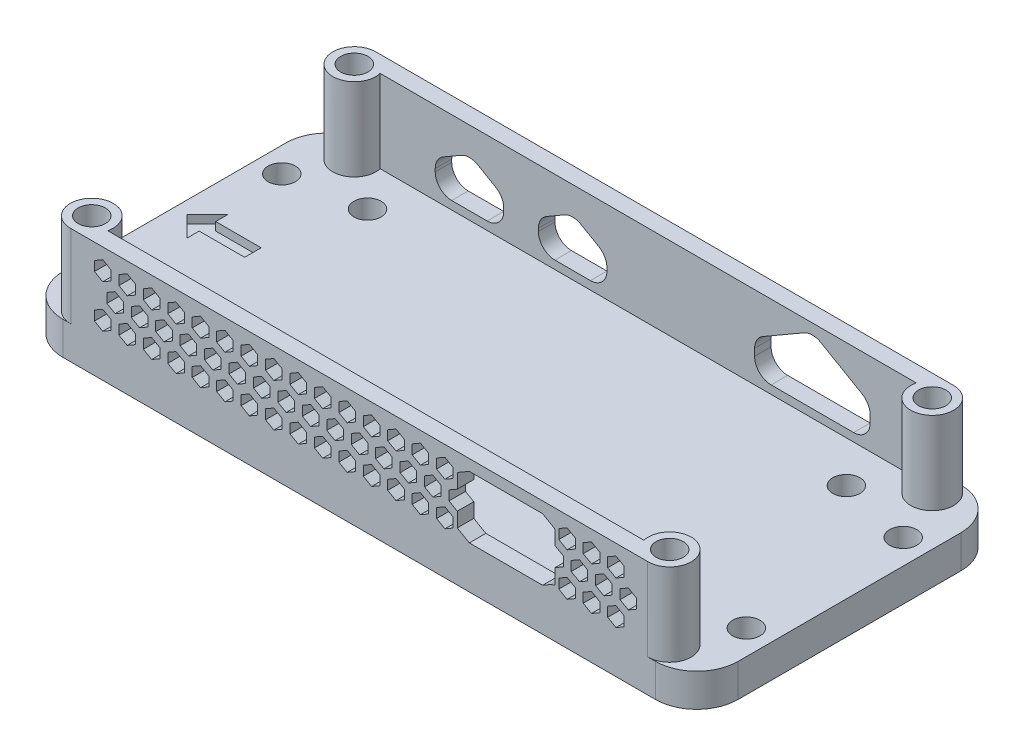
SolidWorks part; units mm, degrees
ref_plane "Płaszczyzna przednia" through (0, 0, 0) normal (0, 0, 1) x (1, 0, 0)
ref_plane "Płaszczyzna górna" through (0, 0, 0) normal (0, 1, 0) x (1, 0, 0)
ref_plane "Płaszczyzna prawa" through (0, 0, 0) normal (1, 0, 0) x (0, 0, -1)
sketch "Szkic1" plane through (0, 0, 0) normal (0, 1, 0) x (1, 0, 0)
  line L0 (-40.885, 0) -> (-37.885, 0) construction
  line L1 (-40.885, -18.5) -> (40.885, -18.5)
  line L2 (-40.885, -18.5) -> (-40.885, 18.5)
  line L3 (-40.885, 18.5) -> (40.885, 18.5)
  line L4 (40.885, -18.5) -> (40.885, 18.5)
  line L5 (-40.885, -18.5) -> (40.885, 18.5) construction
  line L6 (-40.885, 18.5) -> (40.885, -18.5) construction
  line L7 (-37.885, 0) -> (-37.885, 10) construction
  line L8 (-55, 0) -> (55, 0) construction
  line L10 (40.885, 0) -> (37.885, 0) construction
  line L11 (37.885, 0) -> (37.885, 9.5) construction
  circle A2 centre (-37.885, 10) radius 1.65
  circle A3 centre (-37.885, -10) radius 1.65
  circle A6 centre (37.885, 9.5) radius 1.65
  circle A7 centre (37.885, -9.5) radius 1.65
  point P0 (0, 0)
  dimension "D1" = 10
  dimension "D2" = 3.3
  dimension "D6" = 3.3
  dimension "D3" = 3
  dimension "D4" = 37
  dimension "D5" = 75.77
  dimension "D7" = 9.5
extrude "Dodanie-wyciągnięcie1" add sketch "Szkic1" along normal blind 4
fillet "Zaokrąglenie1" radius 5 4 edges at (-40.885, 2, -18.5) (40.885, 2, -18.5) (40.885, 2, 18.5) (-40.885, 2, 18.5)
sketch "Szkic2" plane through (0, 4, 0) normal (0, 1, 0) x (1, 0, 0)
  line L0 (-36.235, 10) -> (36.235, 10) construction
  line L1 (36.235, 9.5) -> (36.235, 10) construction
  line L2 (0, 10) -> (0, 0) construction
  line L4 (-29, 11.5) -> (29, 11.5) construction
  line L5 (-29, 11.5) -> (-29, -11.5) construction
  line L6 (-29, -11.5) -> (29, -11.5) construction
  line L7 (29, 11.5) -> (29, -11.5) construction
  line L8 (-29, 11.5) -> (29, -11.5) construction
  line L9 (-29, -11.5) -> (29, 11.5) construction
  circle A0 centre (-37.885, 10) radius 1.65 construction
  circle A1 centre (29, 11.5) radius 1.65
  circle A2 centre (37.885, 9.5) radius 1.65 construction
  circle A3 centre (29, -11.5) radius 1.65
  circle A4 centre (-29, -11.5) radius 1.65
  circle A5 centre (-29, 11.5) radius 1.65
  dimension "D3" = 3.3
  dimension "D4" = 3.3
  dimension "D5" = 3.3
  dimension "D6" = 3.3
  dimension "D1" = 58
  dimension "D2" = 23
extrude "Wytnij-wyciągnięcie11" cut sketch "Szkic2" against normal blind 3.5
ref_plane "Płaszczyzna2" through (0, 0, -11.5) normal (0, 0, -1) x (-1, 0, 0)
sketch "Szkic4" [suppressed] plane through (0, 0, -11.5) normal (0, 0, -1) x (-1, 0, 0)
  line L0 (-29, 4) -> (-28.7, 4) construction
  line L1 (29, 4) -> (-29, 4) construction
  line L2 (29, 4) -> (-29, 4) construction
  line L3 (-28.7, 4) -> (-28.7, 4.2)
  line L4 (-28.7, 4.2) -> (-25.7, 4.2)
  line L5 (-25.7, 4.2) -> (-27.6, 6.1)
  line L6 (-27.6, 6.1) -> (-27.6, 5.9)
  line L7 (-27.6, 5.9) -> (-27.9, 5.6)
  line L8 (-27.9, 5.6) -> (-27.9, 4)
  line L9 (-27.9, 4) -> (-28.7, 4)
  line L10 (-29, 4) -> (-29, 4.3161) construction
  dimension "D1" = 1.6
  dimension "D3" = 0.2
  dimension "D4" = 1.1
  dimension "D5" = 0.3
  dimension "D6" = 135
  dimension "D7" = 135
  dimension "D8" = 1.1
ref_plane "Płaszczyzna3" through (29, 0, 0) normal (1, 0, 0) x (0, 0, -1)
ref_plane "Płaszczyzna4" through (0, 0, 0) normal (-1, 0, 0) x (0, 0, 1)
sketch "Szkic6" plane through (0, 4, 0) normal (0, 1, 0) x (1, 0, 0)
  line L0 (-34.885, -18.5) -> (-34.885, -16.5)
  line L1 (-35.885, -18.5) -> (35.885, -18.5) construction
  line L2 (-34.885, -16.5) -> (34.885, -16.5)
  line L3 (34.885, -16.5) -> (34.885, -18.5)
  line L4 (34.885, -18.5) -> (-34.885, -18.5)
  line L5 (-40.885, 13.5) -> (-40.885, -13.5) construction
  line L6 (40.885, -13.5) -> (40.885, 13.5) construction
  dimension "D1" = 6
  dimension "D2" = 2
  dimension "D3" = 6
extrude "Dodanie-wyciągnięcie2" add sketch "Szkic6" along normal blind 10
mirror "Lustro4" about plane through (0, 0, 0) normal (0, 0, 1) of "Dodanie-wyciągnięcie2"
sketch "Szkic7" plane through (0, 0, -18.5) normal (0, 0, -1) x (-1, 0, 0)
  line L0 (0, 0) -> (5, 0) construction
  line L1 (-35.885, 0) -> (35.885, 0) construction
  line L2 (5, 0) -> (5, 5) construction
  line L3 (5, 5) -> (5, 14)
  line L4 (34.885, 14) -> (-34.885, 14) construction
  line L6 (25.8, 14) -> (25.8, 5)
  line L10 (17.5, 14) -> (25.8, 14)
  line L11 (5, 14) -> (13.3, 14)
  line L12 (13.3, 14) -> (13.3, 5)
  line L13 (13.3, 5) -> (5, 5)
  line L14 (13.3, 5) -> (17.5, 5) construction
  line L15 (17.5, 5) -> (25.8, 5)
  line L16 (17.5, 14) -> (17.5, 5)
  dimension "D1" = 5
  dimension "D2" = 5
  dimension "D3" = 8.3
  dimension "D4" = 8.3
  dimension "D5" = 4.2
extrude "Wytnij-wyciągnięcie1" cut sketch "Szkic7" against normal up to surface (2 mm away) up to face at (0, 9, -16.5)
sketch "Szkic8" plane through (0, 0, -18.5) normal (0, 0, -1) x (-1, 0, 0)
  line L0 (5, 14) -> (5, 8.5)
  line L1 (5, 14) -> (5, 5) construction
  line L2 (5, 8.5) -> (13.3, 8.5) construction
  line L3 (13.3, 5) -> (13.3, 14) construction
  line L4 (9.15, 8.5) -> (9.15, 10.896) construction
  line L5 (5, 8.5) -> (9.15, 10.896)
  line L6 (9.15, 10.896) -> (13.3, 8.5)
  line L7 (13.3, 8.5) -> (13.3, 14)
  line L8 (13.3, 14) -> (5, 14)
  line L9 (15.4, 14) -> (15.4, 5.5312) construction
  line L10 (17.5, 14) -> (13.3, 14) construction
  line L11 (21.65, 8.5) -> (21.65, 10.896) construction
  line L12 (25.8, 8.5) -> (17.5, 8.5) construction
  line L13 (17.5, 14) -> (25.8, 14)
  line L14 (17.5, 8.5) -> (17.5, 14)
  line L15 (21.65, 10.896) -> (17.5, 8.5)
  line L16 (25.8, 8.5) -> (21.65, 10.896)
  line L17 (25.8, 14) -> (25.8, 8.5)
  dimension "D1" = 30
  dimension "D2" = 5.5
extrude "Dodanie-wyciągnięcie3" add sketch "Szkic8" against normal up to surface (2 mm away) up to face at (-10.2667, 9.3333, -16.5)
fillet "Zaokrąglenie2" radius 2 10 edges at (-25.8, 5, -17.5) (-17.5, 5, -17.5) (-13.3, 5, -17.5) (-5, 5, -17.5) (-21.65, 10.896, -17.5) (-9.15, 10.896, -17.5) (-25.8, 8.5, -17.5) (-17.5, 8.5, -17.5) (-13.3, 8.5, -17.5) (-5, 8.5, -17.5)
sketch "Szkic15" plane through (0, 0, -18.5) normal (0, 0, -1) x (-1, 0, 0)
  line L0 (-34.885, 14) -> (-19.885, 14) construction
  line L1 (34.885, 14) -> (-34.885, 14) construction
  line L2 (-19.885, 14) -> (-19.885, 13.0415) construction
  line L3 (-19.885, 13.0415) -> (-12.885, 9)
  line L4 (-12.885, 9) -> (-12.885, 5)
  line L5 (-12.885, 5) -> (-26.885, 5)
  line L6 (-19.885, 13.0415) -> (-19.885, 5) construction
  line L7 (-26.885, 9) -> (-26.885, 5)
  line L8 (-19.885, 13.0415) -> (-26.885, 9)
  line L9 (-35.885, 0) -> (35.885, 0) construction
  dimension "D1" = 60
  dimension "D2" = 5
  dimension "D3" = 7
  dimension "D4" = 4
  dimension "D5" = 15
extrude "Wytnij-wyciągnięcie6" cut sketch "Szkic15" against normal up to surface (2 mm away) contours L4 L5 L7 L8 L3 up to face at (0, 9, -16.5)
sketch "Szkic11" plane through (0, 4, 0) normal (0, 1, 0) x (1, 0, 0)
  line L0 (0, 0) -> (-35, 0) construction
  line L1 (-35, 0) -> (-35, -15.9) construction
  circle A1 centre (-35, -15.9) radius 2.6
  dimension "D1" = 5.2
  dimension "D3" = 35
  dimension "D2" = 15.9
extrude "Dodanie-wyciągnięcie4" add sketch "Szkic11" along normal up to surface (10 mm away) up to face at (0, 14, 17.5)
sketch "Szkic14" plane through (0, 14, 0) normal (0, 1, 0) x (1, 0, 0)
  circle A0 centre (-35, -15.9) radius 1.65
  dimension "D1" = 3.3
extrude "Wytnij-wyciągnięcie5" cut sketch "Szkic14" against normal blind 4.2
mirror "Lustro6" about plane through (0, 0, 0) normal (0, 0, 1) of "Wytnij-wyciągnięcie5", "Dodanie-wyciągnięcie4"
mirror "Lustro7" about plane through (0, 0, 0) normal (1, 0, 0) of "Lustro6"
sketch "Szkic13" plane through (0, 4, 0) normal (0, 1, 0) x (1, 0, 0)
  line L0 (-40.885, 0) -> (-39.385, 0) construction
  line L1 (-40.885, 13.5) -> (-40.885, -13.5) construction
  line L2 (-39.385, 0) -> (-36.885, 2.5)
  line L3 (-36.885, 2.5) -> (-36.885, 1)
  line L4 (-36.885, 1) -> (-31.385, 1)
  line L5 (-31.385, 1) -> (-31.385, -1)
  line L6 (-36.885, -1) -> (-31.385, -1)
  line L7 (-36.885, -2.5) -> (-36.885, -1)
  line L8 (-39.385, 0) -> (-36.885, -2.5)
  point P10 (-31.385, 0)
  dimension "D1" = 5
  dimension "D2" = 45
  dimension "D3" = 2
  dimension "D4" = 8
  dimension "D5" = 1.5
extrude "Wytnij-wyciągnięcie4" cut sketch "Szkic13" against normal blind 1
fillet "Zaokrąglenie3" radius 2 5 edges at (26.885, 5, -17.5) (26.885, 9, -17.5) (19.885, 13.0415, -17.5) (12.885, 9, -17.5) (12.885, 5, -17.5)
sketch "Szkic18" plane through (0, 0, 18.5) normal (0, 0, 1) x (1, 0, 0)
  line L0 (-31.0702, 14) -> (-31.0702, 11.5) construction
  line L1 (-34.885, 14) -> (34.885, 14) construction
  line L2 (-31.0702, 11.5) -> (-30.5702, 10.634) construction
  line L3 (-31.0702, 10.3453) -> (-30.0702, 10.9226)
  line L4 (-30.0702, 10.9226) -> (-30.0702, 12.0774)
  line L5 (-30.0702, 12.0774) -> (-31.0702, 12.6547)
  line L6 (-31.0702, 12.6547) -> (-32.0702, 12.0774)
  line L7 (-32.0702, 12.0774) -> (-32.0702, 10.9226)
  line L8 (-32.0702, 10.9226) -> (-31.0702, 10.3453)
  line L9 (-30.5702, 10.634) -> (-29.5702, 8.9019) construction
  line L10 (-29.5702, 8.9019) -> (-30.0702, 8.0359) construction
  line L11 (-29.5702, 10.0566) -> (-30.5702, 9.4793)
  line L12 (-30.5702, 9.4793) -> (-30.5702, 8.3246)
  line L13 (-30.5702, 8.3246) -> (-29.5702, 7.7472)
  line L14 (-29.5702, 7.7472) -> (-28.5702, 8.3246)
  line L15 (-28.5702, 8.3246) -> (-28.5702, 9.4793)
  line L16 (-28.5702, 9.4793) -> (-29.5702, 10.0566)
  line L17 (-30.0702, 8.0359) -> (-31.0702, 6.3038) construction
  line L19 (-31.0702, 5.1491) -> (-30.0702, 5.7265)
  line L20 (-30.0702, 5.7265) -> (-30.0702, 6.8812)
  line L21 (-30.0702, 6.8812) -> (-31.0702, 7.4585)
  line L22 (-31.0702, 7.4585) -> (-32.0702, 6.8812)
  line L23 (-32.0702, 6.8812) -> (-32.0702, 5.7265)
  line L24 (-32.0702, 5.7265) -> (-31.0702, 5.1491)
  circle A0 centre (-31.0702, 11.5) radius 1 construction
  circle A1 centre (-29.5702, 8.9019) radius 1 construction
  circle A2 centre (-31.0702, 6.3038) radius 1 construction
  dimension "D1" = 2.5
  dimension "D2" = 2
  dimension "D3" = 2
  dimension "D4" = 3
  dimension "D5" = 3
  dimension "D6" = 2
  dimension "D7" = 1.4
extrude "Wytnij-wyciągnięcie9" cut sketch "Szkic18" against normal up to surface (2 mm away) up to face at (0, 9, 16.5)
pattern_linear "Szyk liniowy1" count 22 spacing 2.96 along (1, 0, 0) of "Wytnij-wyciągnięcie9"
sketch "Szkic19" plane through (0, 0, 18.5) normal (0, 0, 1) x (1, 0, 0)
  line L6 (21.2098, 5.7265) -> (22.2098, 5.1491) construction
  line L7 (22.2098, 5.1491) -> (23.2098, 5.7265) construction
  line L8 (22.2098, 5.1491) -> (23.2098, 5.7265)
  line L12 (22.7098, 8.3246) -> (23.7098, 7.7472) construction
  line L14 (24.7098, 9.4793) -> (23.7098, 10.0566) construction
  line L18 (23.2098, 10.9226) -> (23.2098, 12.0774) construction
  line L19 (23.2098, 12.0774) -> (22.2098, 12.6547)
  line L24 (10.8698, 8.3246) -> (11.8698, 7.7472) construction
  line L25 (10.8698, 8.3246) -> (10.8698, 9.4793)
  line L26 (10.8698, 9.4793) -> (10.8698, 8.3246) construction
  line L27 (10.8698, 9.4793) -> (11.8698, 10.0566)
  line L28 (11.8698, 10.0566) -> (10.8698, 9.4793) construction
  line L29 (13.3298, 12.6547) -> (12.3298, 12.0774)
  line L30 (14.3298, 12.0774) -> (13.3298, 12.6547) construction
  line L31 (13.3298, 12.6547) -> (12.3298, 12.0774) construction
  line L32 (12.3298, 12.0774) -> (12.3298, 10.9226) construction
  line L33 (12.3298, 12.0774) -> (11.8698, 11.8118)
  line L34 (11.8698, 11.8118) -> (11.8698, 10.0566)
  line L35 (13.3298, 12.6547) -> (22.2098, 12.6547)
  line L36 (22.2098, 5.1491) -> (13.3298, 5.1491)
  line L37 (12.3298, 5.7265) -> (13.3298, 5.1491) construction
  line L40 (11.8698, 7.7472) -> (10.8698, 8.3246)
  line L41 (13.3298, 5.1491) -> (12.3298, 5.7265)
  line L42 (12.3298, 5.7265) -> (11.8698, 5.9921)
  line L43 (11.8698, 5.9921) -> (11.8698, 7.7472)
  line L44 (23.2098, 5.7265) -> (23.7098, 5.9045)
  line L45 (23.7098, 5.9045) -> (23.7098, 7.7472)
  line L46 (23.7098, 7.7472) -> (24.7098, 8.3246)
  line L47 (23.7098, 7.7472) -> (24.7098, 8.3246) construction
  line L48 (24.7098, 8.3246) -> (24.7098, 9.4793)
  line L49 (24.7098, 8.3246) -> (24.7098, 9.4793) construction
  line L50 (24.7098, 9.4793) -> (23.7098, 10.0566)
  line L51 (23.2098, 12.0774) -> (23.7098, 11.7887)
  line L52 (23.7098, 11.7887) -> (23.7098, 10.0566)
  point P25 (12.5298, 7.7472)
  point P27 (12.5298, 5.2091)
  point P50 (13.0298, 5.7265)
  point P51 (24.0298, 5.7265)
  point P55 (24.5619, 5.9093)
  point P56 (24.5366, 7.7511)
  point P57 (24.616, 10.4946)
  point P58 (24.0298, 12.0774)
  point P59 (24.7454, 11.7978)
  point P60 (24.5298, 10.0566)
  point P62 (24.5298, 11.8348)
  point P63 (12.5298, 10.0566)
  point P65 (12.5298, 11.7887)
extrude "Wytnij-wyciągnięcie10" cut sketch "Szkic19" against normal up to surface (2 mm away) up to face at (-7.3902, 11.5, 16.5)
